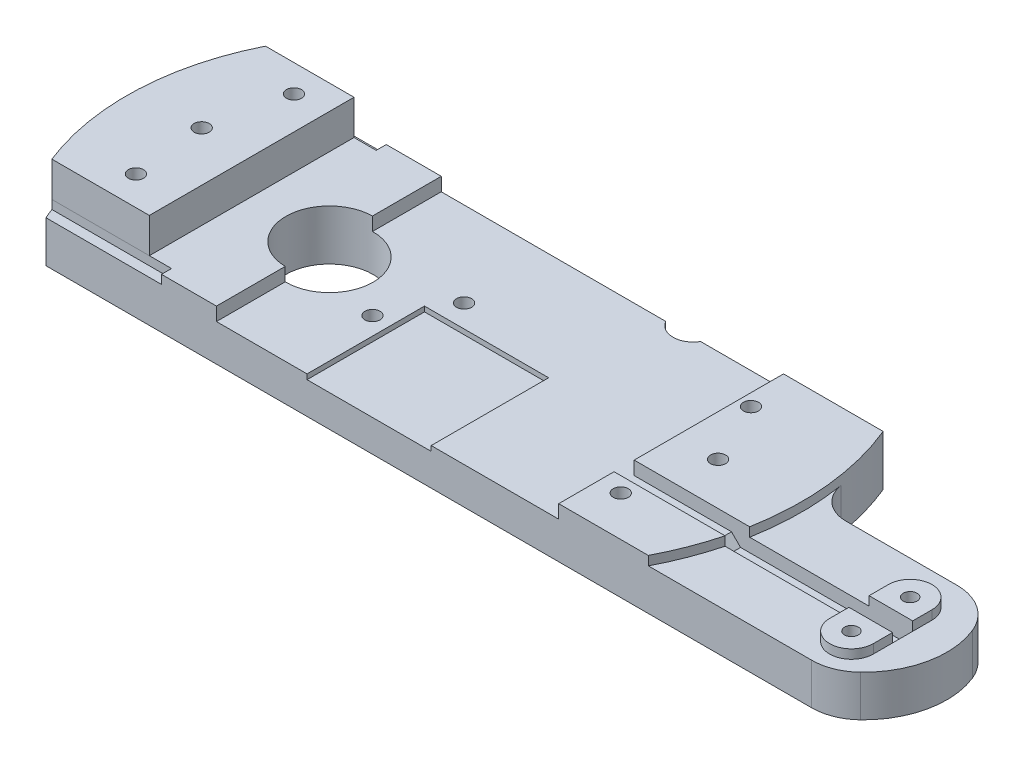
SolidWorks part; units mm, degrees
material "Custom Plastic"
ref_plane "Front Plane" through (0, 0, 0) normal (0, 0, 1) x (1, 0, 0)
ref_plane "Top Plane" through (0, 0, 0) normal (0, 1, 0) x (1, 0, 0)
ref_plane "Right Plane" through (0, 0, 0) normal (1, 0, 0) x (0, 0, -1)
sketch "Sketch1" plane through (0, 0, 0) normal (0, 1, 0) x (1, 0, 0)
  line L1 (-97.5, -33.5) -> (97.5, -33.5)
  line L2 (-97.5, -33.5) -> (-97.5, 33.5)
  line L3 (-97.5, 33.5) -> (97.5, 33.5)
  line L4 (97.5, -33.5) -> (97.5, 33.5)
  line L5 (-97.5, -33.5) -> (97.5, 33.5) construction
  line L6 (-97.5, 33.5) -> (97.5, -33.5) construction
  point P0 (0, 0)
  dimension "D1" = 67
  dimension "D2" = 195
extrude "Boss-Extrude1" add sketch "Sketch1" along normal blind 25.4
sketch "Sketch2" plane through (0, 0, 0) normal (0, -1, 0) x (1, 0, 0)
  line L0 (-97.5, -33.5) -> (-97.5, 33.5) construction
  line L1 (97.5, 33.5) -> (97.5, -33.5) construction
  line L2 (97.5, 33.5) -> (88.5, 33.5)
  line L3 (-97.5, 33.5) -> (97.5, 33.5) construction
  line L4 (97.5, -33.5) -> (91.5, -33.5)
  line L5 (97.5, -33.5) -> (-97.5, -33.5) construction
  line L6 (-97.5, 33.5) -> (-91, 33.5)
  line L7 (-97.5, -33.5) -> (-88, -33.5)
  circle A0 centre (18.0922, -3.2198) radius 79.4078
  circle A1 centre (-22.6589, 2.9929) radius 74.8411
  line M7 (97.5, -33.5) -> (97.5, 33.5)
  line M8 (97.5, 33.5) -> (-97.5, 33.5)
  line M9 (-97.5, 33.5) -> (-97.5, -33.5)
  line M10 (-97.5, -33.5) -> (97.5, -33.5)
  dimension "D1" = 9
  dimension "D2" = 6
  dimension "D3" = 6.5
  dimension "D4" = 9.5
extrude "Cut-Extrude1" cut sketch "Sketch2" against normal through all contours A0 M7 M8 | A0 M10 M7 | A1 M9 M10 | A1 M8 M9 region at (94.8284, 0, 24.4273) region at (95.7123, 0, -25.9883) region at (-95.5654, 0, 25.941) region at (-94.6839, 0, -24.4966)
sketch "Sketch3" plane through (0, 0, 33.5) normal (0, 0, -1) x (-1, 0, 0)
  line L0 (97.5, 25.4) -> (63.2, 25.4)
  line L2 (63.2, 25.4) -> (63.2, 15)
  line L3 (63.2, 15) -> (40.2, 15)
  line L4 (40.2, 15) -> (40.2, 11)
  line L5 (40.2, 11) -> (-61.8, 11)
  line L6 (-91.5, 25.4) -> (88, 25.4) construction
  line L10 (97.5, 0) -> (97.5, 25.4) construction
  line L11 (-61.8, 11) -> (-61.8, 15)
  line L12 (-61.8, 15) -> (-97.5, 15)
  line L13 (-97.5, 25.4) -> (-97.5, 0) construction
  line L14 (-97.5, 15) -> (-97.5, 25.4)
  line L15 (-97.5, 25.4) -> (63.2, 25.4)
  line M13 (-88.5, 0) -> (-88.5, 25.4)
  line M14 (-88.5, 25.4) -> (91, 25.4)
  dimension "D1" = 10.4
  dimension "D2" = 34.3
  dimension "D3" = 23
  dimension "D4" = 4
  dimension "D5" = 102
extrude "Cut-Extrude2" cut sketch "Sketch3" along normal through all contours L11 L12 L2 L3 L4 L5 M13 M14 | L2 L3 L4 L5 L11 L12 L14 L15 region at (12.2699, 18.7206, 33.5)
sketch "Sketch4" plane through (0, 25.4, 0) normal (0, 1, 0) x (1, 0, 0)
  line L0 (-56.5873, 33.5) -> (-56.5873, 30.5)
  line L1 (-63.2, 33.5) -> (-88, 33.5) construction
  line L2 (-56.5873, 30.5) -> (-89.5873, 30.5)
  line L3 (-56.5873, -33.5) -> (-56.5873, -30.5)
  line L4 (-91, -33.5) -> (-63.2, -33.5) construction
  line L5 (-56.5873, -30.5) -> (-92.2617, -30.5)
  line L6 (-56.5873, 33.5) -> (-63.2, 33.5)
  line L7 (-56.5873, -33.5) -> (-63.2, -33.5)
  arc A0 (-88, 33.5) -> (-91, -33.5) centre (-22.6589, -2.9929) ccw construction
  line M5 (-91, -33.5) -> (-63.2, -33.5)
  line M6 (-63.2, -33.5) -> (-63.2, 33.5)
  line M7 (-63.2, 33.5) -> (-88, 33.5)
  arc M8 (-88, 33.5) -> (-91, -33.5) centre (-22.6589, -2.9929) ccw
  dimension "D1" = 3
  dimension "D2" = 3
  dimension "D3" = 33
extrude "Cut-Extrude3" cut sketch "Sketch4" against normal blind 13 contours L2 M6 M7 M8 | L0 L6 L2 M6 | L5 M6 M8 M5 | L7 L3 L5 M6 region at (-59.8937, 25.4, -32) region at (-76.0082, 25.4, -31.9845) region at (-77.4242, 25.4, 31.9889) region at (-59.8937, 25.4, 32)
sketch "Sketch6" plane through (0, 0, 0) normal (0, -1, 0) x (1, 0, 0)
  line L0 (-63.2, -33.5) -> (-97.5, -33.5)
  line L1 (91.5, -33.5) -> (-88, -33.5) construction
  line L2 (-63.2, -33.5) -> (-63.2, 33.5)
  line L3 (-91, 33.5) -> (88.5, 33.5) construction
  line L4 (-63.2, -9) -> (-28.1, -9) construction
  line L5 (-63.2, 8.7) -> (-18.5, 8.7) construction
  line L6 (-63.2, -8.2) -> (-8.1, -8.2) construction
  line L8 (91.5, -33.5) -> (-88, -33.5) construction
  line L9 (-97.5, -33.5) -> (-97.5, 33.5)
  line L10 (-97.5, 33.5) -> (-63.2, 33.5)
  circle A1 centre (-18.5, 8.7) radius 2.25
  circle A2 centre (74.1, -1.7) radius 2.25
  circle A3 centre (68.3, 21.5) radius 2.25
  circle A4 centre (65.4, -20.2) radius 2.25
  circle A5 centre (-8.1, -8.2) radius 2.25
  circle A6 centre (-75.9, 21.8) radius 2.25
  circle A7 centre (-78, 0.1) radius 2.25
  circle A8 centre (-73, -22.4) radius 2.25
  arc A10 (-91, 33.5) -> (-88, -33.5) centre (-22.6589, 2.9929) ccw construction
  dimension "D22" = 4.5
  dimension "D3" = 35.1
  dimension "D4" = 34.3
  dimension "D5" = 44.7
  dimension "D6" = 24.5
  dimension "D7" = 55.1
  dimension "D8" = 42.2
  dimension "D9" = 137.3
  dimension "D10" = 128.6
  dimension "D11" = 131.5
  dimension "D12" = 9.8
  dimension "D13" = 14.8
  dimension "D14" = 12.7
  dimension "D15" = 11.1
  dimension "D16" = 33.6
  dimension "D17" = 55.3
  dimension "D18" = 31.8
  dimension "D19" = 55
  dimension "D20" = 13.3
  dimension "D21" = 25.3
extrude "Cut-Extrude4" cut sketch "Sketch6" against normal through all contours A5 | A1 | A6 | A7 | A8 | A4 | A2 | A3 region at (-18.5, 0, 8.7) region at (74.1, 0, -1.7) region at (68.3, 0, 21.5) region at (65.4, 0, -20.2) region at (-8.1, 0, -8.2) region at (-75.9, 0, 21.8) region at (-78, 0, 0.1) region at (-73, 0, -22.4)
sketch "Sketch7" plane through (0, 11, 0) normal (0, 1, 0) x (1, 0, 0)
  line L1 (-13.2, 1.5) -> (23.8, 1.5)
  line L2 (-13.2, 1.5) -> (-13.2, -33.5)
  line L3 (-13.2, -33.5) -> (23.8, -33.5)
  line L4 (23.8, 1.5) -> (23.8, -33.5)
  line L8 (-63.2, 30.5) -> (-63.2, -30.5) construction
  line L9 (-63.2, 30.5) -> (-63.2, -30.5) construction
  line L10 (-40.2, -33.5) -> (61.8, -33.5) construction
  dimension "D1" = 50
  dimension "D2" = 87
  dimension "D3" = 35
extrude "Cut-Extrude5" cut sketch "Sketch7" against normal blind 1.5
sketch "Sketch8" plane through (0, 25.4, 0) normal (0, 1, 0) x (1, 0, 0)
  line L0 (-56.5873, -33.5) -> (-97.5, -33.5)
  line L1 (-97.5, -33.5) -> (-97.5, 33.5)
  line L3 (-97.5, 33.5) -> (31.9, 33.5)
  line L6 (31.9, 36.5) -> (31.9, 30.5)
  line L7 (31.9, 33.5) -> (37.0962, 33.5)
  line L10 (-56.5873, 33.5) -> (-88, 33.5) construction
  line L11 (-40.2, 33.5) -> (61.8, 33.5) construction
  circle A1 centre (31.9, 36.5) radius 6
  arc A2 (-89.5873, 30.5) -> (-92.2617, -30.5) centre (-22.6589, -2.9929) ccw construction
  dimension "D1" = 12
  dimension "D2" = 129.4
extrude "Cut-Extrude6" cut sketch "Sketch8" against normal blind 18.5 contours L6 A1 L7 | L3 A1 L6 region at (29.8648, 25.4, -32.2699) region at (33.9352, 25.4, -32.2699)
sketch "Sketch9" plane through (0, 0, 0) normal (0, -1, 0) x (1, 0, 0)
  line L0 (88.5, 33.5) -> (137.2004, 33.5)
  line L1 (139.5727, -7.5) -> (97.3846, -7.5)
  arc A0 (153.4738, 1.8643) -> (147.5429, 29.3643) centre (130.3054, 11.2571) ccw
  arc A1 (91.5, -33.5) -> (88.5, 33.5) centre (18.0922, -3.2198) ccw construction
  arc A2 (142.3827, -10.6321) -> (147.5429, 29.3643) centre (130.3054, 11.2571) ccw construction
  arc A3 (147.5429, 29.3643) -> (137.2004, 33.5) centre (137.2004, 18.5) ccw
  arc A4 (147.5429, 29.3643) -> (137.9704, 33.4802) centre (137.2004, 18.5) ccw construction
  arc A5 (139.5727, -7.5) -> (153.4738, 1.8643) centre (139.5727, 7.5) ccw
  circle A6 centre (112.8181, -27.5) radius 16 construction
  circle A7 centre (103.4238, 59.4942) radius 16 construction
  circle A8 centre (112.8181, -27.5) radius 20 construction
  arc A9 (97.3846, -7.5) -> (88.5, 33.5) centre (18.0922, -3.2198) ccw
  circle A10 centre (138.3, 5.25) radius 2.05
  circle A11 centre (138.3, 22.75) radius 2.05
  circle A12 centre (138.3, 22.75) radius 2.05 construction
  circle A13 centre (138.3, 5.25) radius 2.05 construction
  dimension "D1" = 4
extrude "Boss-Extrude2" add sketch "Sketch9" against normal offset from surface (12.3 mm away) 1.3 up to face at (-16.25, 11, 8.7) offset beyond the face yes
fillet "Fillet1" radius 10 1 edges at (97.3846, 6.15, -7.5)
sketch "Sketch10" plane through (0, 0, 0) normal (0, -1, 0) x (1, 0, 0)
  circle A0 centre (-40.0178, 0) radius 13
  dimension "D1" = 26
extrude "Cut-Extrude7" cut sketch "Sketch10" against normal through all
sketch "Sketch11" plane through (0, 12.3, 0) normal (0, 1, 0) x (1, 0, 0)
  line L0 (138.3, -5.25) -> (138.3, -22.75) construction
  line L1 (144.8, -5.25) -> (144.8, -22.75)
  line L2 (131.8, -5.25) -> (131.8, -22.75)
  line L3 (131.8, -11) -> (144.8, -11)
  line L4 (131.8, -17) -> (144.8, -17)
  line L5 (131.8, -14) -> (144.8, -14) construction
  arc A0 (144.8, -5.25) -> (131.8, -5.25) centre (138.3, -5.25) ccw
  arc A1 (131.8, -22.75) -> (144.8, -22.75) centre (138.3, -22.75) ccw
  point P4 (138.3, -14)
  circle M15 centre (138.3, -22.75) radius 2.05
  circle M16 centre (138.3, -5.25) radius 2.05
  dimension "D1" = 13
  dimension "D2" = 6
extrude "Boss-Extrude3" add sketch "Sketch11" along normal up to surface (2.7 mm away) contours L1 A0 L2 L3 M16 | L2 A1 L1 L4 M15 region at (144.6214, 12.3, 8.125) region at (144.6214, 12.3, 19.875) up to face at (70.55, 15, 21.5)
sketch "Sketch12" plane through (0, 0, 11) normal (0, 0, 1) x (1, 0, 0)
  line L0 (144.8, 15) -> (144.8, 8.3)
  line L1 (144.8, 8.3) -> (93.5, 8.3)
  line L3 (97.5, 12.3) -> (88.5, 12.3) construction
  line L4 (90.8, 11) -> (61.8, 11)
  line L5 (61.8, 11) -> (61.8, 15)
  line L6 (61.8, 15) -> (88.5, 15) construction
  line L7 (61.8, 15) -> (144.8, 15)
  line L10 (97.5, 12.3) -> (93.5, 12.3) construction
  line L12 (88.5, 12.3) -> (137.2004, 12.3) construction
  line L13 (93.5, 12.3) -> (93.5, 8.3) construction
  line L14 (61.8, 11) -> (61.8, 15) construction
  line L15 (23.8, 11) -> (61.8, 11) construction
  line L16 (93.5, 8.3) -> (90.8, 11)
  dimension "D1" = 45
extrude "Cut-Extrude8" cut sketch "Sketch12" along normal up to surface (6 mm away) up to face at (138.3, 13.65, 17)
split "Split1" bodies to split 116 resulting bodies 114 115 split by face at (-52.6367, 15, 0)
